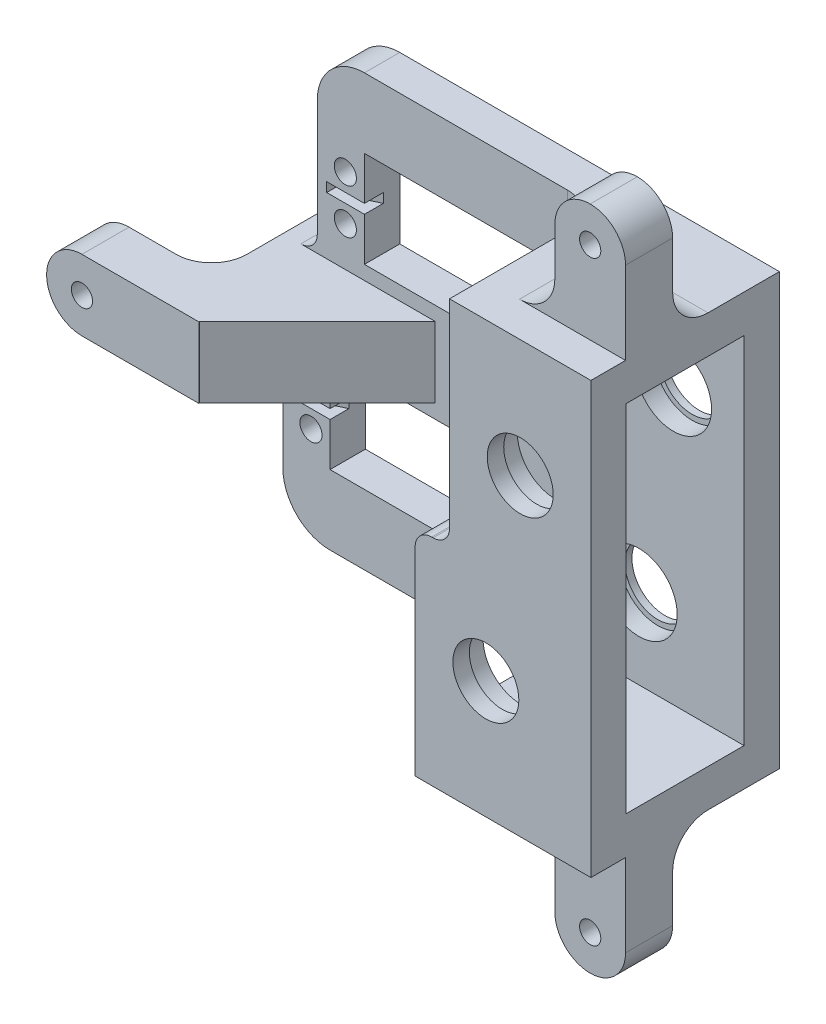
SolidWorks part; units mm, degrees
ref_plane "Front Plane" through (0, 0, 0) normal (0, 0, 1) x (1, 0, 0)
ref_plane "Top Plane" through (0, 0, 0) normal (0, 1, 0) x (1, 0, 0)
ref_plane "Right Plane" through (0, 0, 0) normal (1, 0, 0) x (0, 0, -1)
sketch "Sketch1" plane through (0, 0, 0) normal (0, 0, 1) x (1, 0, 0)
  line L0 (-15, 0) -> (22.2932, 0)
  line L5 (-15, 91.3619) -> (22.2932, 91.3619)
  line L6 (-15, 0) -> (-15, 91.3619)
  line L7 (22.2932, 0) -> (22.2932, 91.3619)
  line L8 (0, 25) -> (7.2932, 66.3619) construction
  line L9 (0, 25) -> (0, 79.2) construction
  circle A1 centre (0, 25) radius 8.1
  circle A2 centre (7.2932, 66.3619) radius 8.1
  point P4 (0, 0)
  dimension "D2" = 16.2
  dimension "D5" = 25
  dimension "D4" = 15
  dimension "D6" = 25
  dimension "D8" = 42
  dimension "D9" = 10
  dimension "D10" = 15
extrude "Boss-Extrude1" add sketch "Sketch1" along normal blind 40
ref_plane "INNER WALL" through (0, 0, 39) normal (0, 0, 1) x (1, 0, 0)
ref_plane "OUTER WALL" through (0, 0, 32.65) normal (0, 0, 1) x (1, 0, 0)
sketch "Sketch2" plane through (0, 0, 0) normal (0, 1, 0) x (1, 0, 0)
  line L1 (-15, -7.5) -> (22.2932, -7.5)
  line L2 (-15, -7.5) -> (-15, -32.5)
  line L3 (-15, -32.5) -> (22.2932, -32.5)
  line L4 (22.2932, -7.5) -> (22.2932, -32.5)
  line L6 (-15, -40) -> (-15, 0) construction
  line L7 (22.2932, -40) -> (22.2932, 0) construction
  point P9 (22.2932, -20)
  point P10 (22.2932, -20)
  dimension "D1" = 25
extrude "Cut-Extrude1" cut sketch "Sketch2" along normal through all from offset 8
sketch "Sketch10" plane through (0, 0, 40) normal (0, 0, 1) x (1, 0, 0)
  circle A0 centre (7.2932, 66.3619) radius 8.1
  circle A1 centre (0, 25) radius 10.837
  circle A2 centre (7.2932, 66.3619) radius 7
  circle A3 centre (0, 25) radius 7
  circle A4 centre (7.2932, 66.3619) radius 8.1 construction
  circle A5 centre (0, 25) radius 8.1 construction
  dimension "D2" = 14
  dimension "D4" = 14
extrude "Boss-Extrude2" add sketch "Sketch10" against normal offset from surface (3.5 mm away) 4 up to face at (-8.1, 25, 32.5)
sketch "Sketch11" plane through (0, 0, 0) normal (0, 0, -1) x (-1, 0, 0)
  circle A0 centre (-7.2932, 66.3619) radius 8.1
  circle A1 centre (-7.2932, 66.3619) radius 7
  circle A2 centre (0, 25) radius 8.1
  circle A3 centre (0, 25) radius 7
  circle A4 centre (0, 25) radius 8.1 construction
  circle A5 centre (-7.2932, 66.3619) radius 8.1 construction
  dimension "D1" = 14
  dimension "D2" = 14
extrude "Boss-Extrude3" add sketch "Sketch11" against normal offset from surface (3.5 mm away) 4 up to face at (8.1, 25, 7.5)
ref_axis "Axis1" through (0, 25, 3.5) along (0, 0, -1)
ref_plane "Plane1" through (0, 25, 0) normal (0, -1, 0) x (-1, 0, 0)
ref_axis "Axis2" through (7.2932, 66.3619, 3.5) along (0, 0, -1)
ref_plane "Plane2" through (0, 66.3619, 0) normal (0, -1, 0) x (-1, 0, 0)
sketch "Sketch12" plane through (0, 0, 0) normal (0, 0, -1) x (-1, 0, 0)
  line L0 (-20.5113, 25) -> (20.5113, 25) construction
  line L1 (15, 0) -> (75.56, 0)
  line L2 (15, 0) -> (15, 91.3619)
  line L3 (15, 91.3619) -> (68.2668, 91.3619)
  line L5 (-20.5113, 66.3619) -> (20.5113, 66.3619) construction
  line L6 (24.66, 35.2) -> (65.56, 35.2)
  line L7 (24.66, 35.2) -> (24.66, 14.8)
  line L8 (24.66, 14.8) -> (65.56, 14.8)
  line L9 (65.56, 35.2) -> (65.56, 14.8)
  line L10 (-22.2932, 91.3619) -> (15, 91.3619) construction
  line L11 (17.3668, 76.5619) -> (58.2668, 76.5619)
  line L12 (17.3668, 76.5619) -> (17.3668, 56.1619)
  line L13 (17.3668, 56.1619) -> (58.2668, 56.1619)
  line L14 (58.2668, 76.5619) -> (58.2668, 56.1619)
  line L16 (15, 0) -> (-22.2932, 0) construction
  line L17 (15, 91.3619) -> (15, 0) construction
  line L18 (68.2668, 91.3619) -> (68.2668, 45.681)
  line L19 (68.2668, 45.681) -> (75.56, 45.681)
  line L20 (75.56, 45.681) -> (75.56, 0)
  line L21 (58.2668, 56.1619) -> (58.2668, 35.2) construction
  line L22 (45.11, 35.2) -> (45.11, 14.8) construction
  line L32 (37.8168, 76.5619) -> (37.8168, 56.1619) construction
  circle A0 centre (35, 25) radius 6.6 construction
  circle A1 centre (0, 25) radius 7 construction
  circle A2 centre (27.7068, 66.3619) radius 6.6 construction
  circle A3 centre (-7.2932, 66.3619) radius 7 construction
  point P15 (45.11, 14.8)
  point P17 (58.2668, 45.681)
  point P27 (17.3668, 66.3619)
  point P34 (37.8168, 56.1619)
  point P53 (45.11, 25)
  dimension "D7" = 13.2
  dimension "D11" = 13.2
  dimension "D2" = 20.4
  dimension "D3" = 40.9
  dimension "D4" = 10.11
  dimension "D9" = 10.11
  dimension "D5" = 35
  dimension "D6" = 10
  dimension "D8" = 10
extrude "Boss-Extrude4" add sketch "Sketch12" against normal up to surface (7.5 mm away) up to face at (8.1, 25, 7.5)
sketch "Sketch13" plane through (0, 0, 0) normal (0, 0, -1) x (-1, 0, 0)
  line L0 (24.66, 35.2) -> (24.66, 14.8) construction
  line L1 (-20.5113, 25) -> (20.5113, 25) construction
  line L2 (65.56, 14.8) -> (65.56, 35.2) construction
  line L3 (17.3668, 76.5619) -> (17.3668, 56.1619) construction
  line L5 (-20.5113, 66.3619) -> (20.5113, 66.3619) construction
  line L6 (58.2668, 56.1619) -> (58.2668, 76.5619) construction
  circle A0 centre (20.61, 29.75) radius 2.3495
  circle A1 centre (20.61, 20.25) radius 2.3495
  circle A2 centre (69.61, 29.75) radius 2.3495
  circle A3 centre (69.61, 20.25) radius 2.3495
  circle A4 centre (13.3168, 71.1119) radius 2.3495
  circle A5 centre (13.3168, 61.6119) radius 2.3495
  circle A6 centre (62.3168, 71.1119) radius 2.3495
  circle A7 centre (62.3168, 61.6119) radius 2.3495
  dimension "D1" = 4.699
  dimension "D2" = 4.05
  dimension "D3" = 9.5
  dimension "D4" = 4.75
  dimension "D5" = 4.05
  dimension "D7" = 9.5
  dimension "D8" = 4.05
  dimension "D9" = 4.75
  dimension "D10" = 4.05
extrude "Cut-Extrude2" cut sketch "Sketch13" against normal up to next
sketch "Sketch22" plane through (0, 0, 7.5) normal (0, 0, 1) x (1, 0, 0)
  line L0 (-58.2668, 56.1619) -> (-58.2668, 76.5619) construction
  line L1 (-58.2668, 65.3619) -> (-66.2668, 65.3619)
  line L2 (-58.2668, 65.3619) -> (-58.2668, 67.3619)
  line L3 (-58.2668, 67.3619) -> (-66.2668, 67.3619)
  line L4 (-66.2668, 65.3619) -> (-66.2668, 67.3619)
  line L5 (-17.3668, 76.5619) -> (-17.3668, 56.1619) construction
  line L6 (-17.3668, 65.3619) -> (-9.3668, 65.3619)
  line L7 (-17.3668, 65.3619) -> (-17.3668, 67.3619)
  line L8 (-17.3668, 67.3619) -> (-9.3668, 67.3619)
  line L9 (-9.3668, 65.3619) -> (-9.3668, 67.3619)
  line L10 (-24.66, 35.2) -> (-24.66, 14.8) construction
  line L11 (-24.66, 24) -> (-16.66, 24)
  line L12 (-24.66, 24) -> (-24.66, 26)
  line L13 (-24.66, 26) -> (-16.66, 26)
  line L14 (-16.66, 24) -> (-16.66, 26)
  line L15 (-65.56, 14.8) -> (-65.56, 35.2) construction
  line L16 (-65.56, 24) -> (-73.56, 24)
  line L17 (-65.56, 24) -> (-65.56, 26)
  line L18 (-65.56, 26) -> (-73.56, 26)
  line L19 (-73.56, 24) -> (-73.56, 26)
  point P24 (-58.2668, 66.3619)
  point P25 (-66.2668, 66.3619)
  point P26 (-73.56, 25)
  point P27 (-65.56, 25)
  dimension "D1" = 2
  dimension "D2" = 8
extrude "Cut-Extrude6" cut sketch "Sketch22" against normal blind 2
sketch "Sketch14" plane through (0, 0, 7.5) normal (0, 0, 1) x (1, 0, 0)
  line L0 (22.2932, 0) -> (22.2932, 91.3619) construction
  line L1 (22.2932, 91.3619) -> (-15, 91.3619)
  line L2 (22.2932, 91.3619) -> (22.2932, 83.3619)
  line L3 (22.2932, 83.3619) -> (-15, 83.3619)
  line L4 (-15, 91.3619) -> (-15, 83.3619)
  line L5 (22.2932, 91.3619) -> (-15, 91.3619) construction
  line L6 (-15, 91.3619) -> (-15, 0) construction
  dimension "D1" = 8
extrude "Boss-Extrude5" add sketch "Sketch14" along normal up to surface (25 mm away) up to face at (-8.1, 25, 32.5)
sketch "Sketch18" plane through (0, 0, 40) normal (0, 0, 1) x (1, 0, 0)
  line L0 (7.2932, 66.3619) -> (7.2932, 25) construction
  line L1 (-15, 91.3619) -> (-7.7068, 91.3619)
  line L2 (-15, 91.3619) -> (-15, 45.681)
  line L3 (-15, 45.681) -> (-7.7068, 45.681)
  line L4 (-7.7068, 91.3619) -> (-7.7068, 45.681)
  line L5 (0, 25) -> (7.2932, 25) construction
  circle A0 centre (7.2932, 66.3619) radius 8.1 construction
  point P13 (7.2932, 45.681)
  dimension "D1" = 15
extrude "Cut-Extrude4" cut sketch "Sketch18" against normal up to surface (32.5 mm away) up to face at (-45.11, 25, 7.5)
sketch "Sketch15" plane through (0, 0, 0) normal (0, 0, -1) x (-1, 0, 0)
  circle A0 centre (0, 25) radius 11
  circle A1 centre (-7.2932, 66.3619) radius 11
  dimension "D1" = 22
extrude "Cut-Extrude3" cut sketch "Sketch15" against normal blind 2
sketch "Sketch19" plane through (0, 0, 32.65) normal (0, 0, 1) x (1, 0, 0)
  line L1 (22.2932, 91.3619) -> (7.2932, 91.3619)
  line L2 (22.2932, 91.3619) -> (22.2932, 116.3619)
  line L3 (22.2932, 116.3619) -> (7.2932, 116.3619)
  line L4 (7.2932, 91.3619) -> (7.2932, 116.3619)
  line L5 (22.2932, 0) -> (7.2932, 0)
  line L6 (22.2932, 0) -> (22.2932, -25)
  line L7 (22.2932, -25) -> (7.2932, -25)
  line L8 (7.2932, 0) -> (7.2932, -25)
  line L9 (-15, 0) -> (22.2932, 0) construction
  dimension "D1" = 15
  dimension "D2" = 25
extrude "Boss-Extrude6" add sketch "Sketch19" against normal blind 10
sketch "Sketch20" plane through (0, 0, 32.65) normal (0, 0, 1) x (1, 0, 0)
  line L0 (-15, 45.681) -> (-7.7068, 45.681) construction
  line L1 (-100.56, 38.181) -> (-68.2668, 38.181)
  line L2 (-100.56, 38.181) -> (-100.56, 53.181)
  line L3 (-100.56, 53.181) -> (-68.2668, 53.181)
  line L4 (-68.2668, 38.181) -> (-68.2668, 53.181)
  line L5 (-75.56, 0) -> (-75.56, 45.681) construction
  line L6 (-68.2668, 45.681) -> (-68.2668, 91.3619) construction
  point P4 (-68.2668, 45.681)
  dimension "D1" = 25
  dimension "D2" = 15
extrude "Boss-Extrude7" add sketch "Sketch20" against normal blind 10 separate body
sketch "Sketch21" plane through (0, 0, 22.65) normal (0, 0, -1) x (-1, 0, 0)
  line L0 (100.56, 38.181) -> (68.2668, 38.181) construction
  line L1 (68.2668, 53.181) -> (75.56, 53.181)
  line L2 (68.2668, 53.181) -> (68.2668, 38.181)
  line L3 (68.2668, 38.181) -> (75.56, 38.181)
  line L4 (75.56, 53.181) -> (75.56, 38.181)
  line L5 (75.56, 0) -> (75.56, 45.681) construction
extrude "Boss-Extrude8" add sketch "Sketch21" along normal up to surface (22.65 mm away) up to face at (-11, 25, 0)
chamfer "Chamfer2" distance 2 angle 65 4 edges at (-65.56, 25, 5.5) (-58.2668, 66.3619, 5.5) (-17.3668, 66.3619, 5.5) (-24.66, 25, 5.5) first distance on face at (-65.56, 25, 5.125) first distance on face at (-58.2668, 66.3619, 5.125) first distance on face at (-17.3668, 66.3619, 5.125) first distance on face at (-24.66, 25, 5.125)
fillet "Fillet1" radius 7.5 13 edges at (-100.56, 53.181, 27.65) (-100.56, 38.181, 27.65) (-75.56, 45.681, 22.65) (7.2932, 116.3619, 27.65) (22.2932, 116.3619, 27.65) (7.2932, -25, 27.65) (22.2932, -25, 27.65) (14.7932, 0, 22.65) (14.7932, 91.3619, 22.65) (7.2932, 0, 27.65) (7.2932, 91.3619, 27.65) (-7.7068, 87.3619, 7.5) (-15, 4, 7.5)
chamfer "Chamfer1" distance 25 angle 45 1 edges at (-68.2668, 45.681, 7.5)
hole_wizard "M4 Clearance Hole1" positions "Sketch23" profile "Sketch24" hole size "M4" standard "ANSI Metric" end condition through all
sketch "Sketch23" plane through (0, 0, 22.65) normal (0, 0, -1) x (-1, 0, 0)
  point P0 (-14.7932, 108.8619)
  point P3 (93.06, 45.681)
  point P6 (-14.7932, -17.5)
sketch "Sketch24" plane through (14.7932, 108.8619, 22.65) normal (1, 0, 0) x (0, 1, 0)
  line L0 (0, 0) -> (0, 17.35)
  line L1 (0, 17.35) -> (2.25, 17.35)
  line L2 (2.25, 17.35) -> (2.25, 0.025)
  line L3 (2.25, 0.025) -> (2.275, 0)
  line L5 (2.275, 0) -> (0, 0)
  line L6 (-2.25, 0.025) -> (-2.275, 0) construction
  line L11 (0, -6.35) -> (0, 107.95) construction
  dimension "Thru Hole Dia." = 4.5
  dimension "Thru Hole Depth" = 17.35
  dimension "Near C'Sink Dia." = 4.55
  dimension "Near C'Sink Angle" = 90
fillet "Fillet2" radius 10 2 edges at (-75.56, 0, 3.75) (-68.2668, 91.3619, 3.75)
fillet "Fillet3" radius 3.5 3 edges at (-15, 45.681, 36.25) (-7.7068, 45.681, 36.25) (-68.2668, 53.181, 3.75)
equation "\"D4@Sketch13\"=\"D3@Sketch13\"/2"
equation "\"D5@Sketch12\"=\"D1@Sketch12\""
equation "\"D8@Sketch13\"=\"D2@Sketch13\""
equation "\"D9@Sketch13\"=\"D7@Sketch13\"/2"
equation "\"D10@Sketch13\"=\"D5@Sketch13\""
